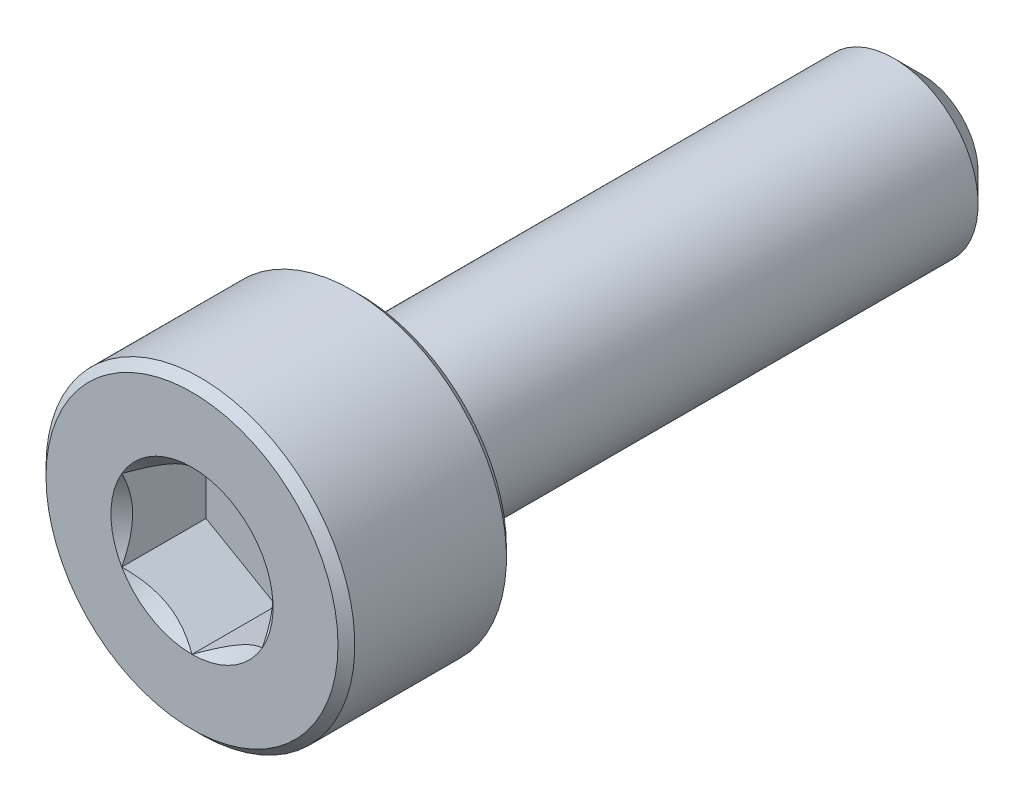
SolidWorks part; units mm, degrees
ref_plane "Front Plane" through (0, 0, 0) normal (0, 0, 1) x (1, 0, 0)
ref_plane "Top Plane" through (0, 0, 0) normal (0, 1, 0) x (1, 0, 0)
ref_plane "Right Plane" through (0, 0, 0) normal (1, 0, 0) x (0, 0, -1)
sketch "Sketch1" plane through (0, 0, 0) normal (1, 0, 0) x (0, 0, -1)
  line L0 (-6.5, 0) -> (6.5, 0) construction
  line L1 (6.5, 0) -> (6.5, 1) construction
  line L2 (6.5, 1) -> (6, 1.5) construction
  line L3 (6, 1.5) -> (-3.5, 1.5) construction
  line L5 (-3.5, 1.5) -> (-3.5, 2.75) construction
  line L6 (-3.5, 2.75) -> (-6.5, 2.75) construction
  line L7 (-6.5, 2.75) -> (-6.5, 0) construction
  line L8 (6.5, 1) -> (6.5, 1.5) construction
  line L9 (6.4688, 1.5541) -> (6.7188, 1.1211) construction
  line L10 (6.7188, 1.1211) -> (6.9688, 1.5541) construction
  line L11 (6.9688, 1.5541) -> (6.4688, 1.5541) construction
  line L12 (6.7188, 1.5541) -> (6.7188, 1.5) construction
  line L13 (6.7188, 1.1211) -> (6.7188, 1.1752) construction
  line L14 (6.6875, 1.1752) -> (6.75, 1.1752) construction
  line L15 (6.5, 1.5) -> (6.9375, 1.5) construction
  line L16 (6.4844, 1.5271) -> (6.9531, 1.5271) construction
  line L17 (6.5, 0) -> (6.5, -1.5) construction
  line L18 (-3.65, 2.75) -> (-3.5, 2.6) construction
  line L19 (-6.35, 2.75) -> (-6.5, 2.6) construction
  point P0 (-6.5, 1.25)
  point P3 (4.75, 1.5)
  point P4 (0, 0)
  point P22 (6.7188, 1.1752)
  point P24 (-3.5, 1.5)
  point P25 (6.7188, 1.5)
  point P28 (6.7188, 1.5271)
  point P29 (4.75, -1.5)
  point P31 (-5, 2.75)
  point P37 (-4.025, 2.75)
  point P38 (-6.275, 2.75)
  point P41 (-5, 0)
  dimension "head height" = 3
  dimension "D1" = 45
  dimension "Head Diameter" = 5.5
  dimension "Thread Size" = 3
  dimension "drive size" = 2.5
  dimension "Thread Pitch" = 0.5
  dimension "D2" = 0.0625
  dimension "D3" = 0.5
  dimension "D4" = 1.75
  dimension "D7" = 0.15
  dimension "D8" = 0.15
  dimension "D9" = 0.15
  dimension "D10" = 0.075
  dimension "D11" = 0.375
  dimension "length" = 10
  dimension "Drive Depth" = 1.5
sketch "Sketch2" plane through (0, 0, 0) normal (1, 0, 0) x (0, 0, -1)
  line L1 (-6.35, 2.75) -> (-3.65, 2.75)
  line L4 (6, 1.5) -> (6.5, 1)
  line L5 (6.5, 1) -> (6.5, 0)
  line L6 (-3.65, 2.75) -> (-3.5, 2.6) construction
  line L7 (6.5, 0) -> (-6.5, 0)
  line L8 (-6.35, 2.75) -> (-6.5, 2.6) construction
  line L9 (-3.65, 2.75) -> (-3.5, 2.6)
  line L10 (-6.35, 2.75) -> (-6.5, 2.6)
  line L11 (-6.5, 2.6) -> (-6.5, 0)
  line L12 (-3.5, 2.6) -> (-3.5, 1.5)
  line L13 (-3.5, 1.5) -> (6, 1.5)
revolve "Revolve1" add sketch "Sketch2" angle 360 about L7
sketch "Sketch3" plane through (0, 0, 6.5) normal (0, 0, 1) x (1, 0, 0)
  line L1 (0, 1.4434) -> (-1.25, 0.7217)
  line L2 (-1.25, 0.7217) -> (-1.25, -0.7217)
  line L3 (-1.25, -0.7217) -> (0, -1.4434)
  line L4 (0, -1.4434) -> (1.25, -0.7217)
  line L5 (1.25, -0.7217) -> (1.25, 0.7217)
  line L6 (1.25, 0.7217) -> (0, 1.4434)
  circle A0 centre (0, 0) radius 1.25 construction
  dimension "D1" = 2.5
extrude "Cut-Extrude1" cut sketch "Sketch3" against normal up to vertex (1.5 mm away) up to point (0, 0, 5)
sketch "Sketch4" plane through (0, 0, 6.5) normal (0, 0, 1) x (1, 0, 0)
  circle A0 centre (0, 0) radius 1.4434
extrude "Cut-Extrude2" cut sketch "Sketch4" against normal blind 0.5 draft 45
ref_plane "Plane1" [suppressed] through (0, 0, 3.5) normal (0, 0, 1) x (1, 0, 0)
split "Split1" [suppressed] bodies to split 106
sketch "Sketch6" [suppressed] plane through (0, 0, -6.5) normal (0, 0, -1) x (-1, 0, 0)
  circle A0 centre (0, 0) radius 1.5
curve "Helix/Spiral1" [suppressed] pitch 0.5 height 10.5 turns 21
sketch "Sketch7" [suppressed] plane through (0, 0, 0) normal (1, 0, 0) x (0, 0, -1)
  line L0 (6.4844, 1.5271) -> (6.9531, 1.5271)
  line L1 (6.9531, 1.5271) -> (6.75, 1.1752)
  line L2 (6.75, 1.1752) -> (6.6875, 1.1752)
  line L3 (6.6875, 1.1752) -> (6.4844, 1.5271)
sweep "Cut-Sweep1" [suppressed] cut profiles "Sketch7" path "Helix/Spiral1"
sketch "Sketch8" [suppressed] plane through (0, 0, 3.5) normal (0, 0, -1) x (-1, 0, 0)
  circle A0 centre (0, 0) radius 1.5
extrude "Boss-Extrude1" [suppressed] add sketch "Sketch8" along normal through all draft 45
ref_plane "Plane2" [suppressed] through (0, 0, 5) normal (0, 0, 1) x (1, 0, 0)
sketch "Sketch9" [suppressed] plane through (0, 0, 5) normal (0, 0, 1) x (1, 0, 0)
  line L0 (0, 2.6744) -> (0.072, 2.7491)
  line L1 (0, 2.6744) -> (-0.072, 2.7491)
  line L2 (0, 2.75) -> (0, 0) construction
  line L3 (-0.072, 2.7491) -> (0, 0) construction
  line L4 (0, 0) -> (0.072, 2.7491) construction
  arc A0 (0.072, 2.7491) -> (-0.072, 2.7491) centre (0, 0) ccw
  circle A1 centre (0, 0) radius 2.6744 construction
  dimension "D1" = 5.5
  dimension "D2" = 5.3487
  dimension "D3" = 3
extrude "Cut-Extrude4" [suppressed] cut sketch "Sketch9" against normal up to vertex and the other way up to vertex
pattern_circular "CirPattern2" [suppressed] count 96 over 360 about axis through (0, 0, 6.5) along (0, 0, -1) of bodies 113
equation "\"D2@Sketch1\" = \"Thread Pitch@Sketch1\" / 8"
equation "\"D3@Sketch1\" = \"Thread Pitch@Sketch1\""
equation "\"D3@Helix/Spiral1\" = \"length@Sketch1\" + \"Thread Pitch@Sketch1\""
equation "\"D4@Helix/Spiral1\" = \"Thread Pitch@Sketch1\""
equation "\"D4@Sketch1\" = \"Thread Pitch@Sketch1\" * 3.5"
equation "\"D7@Sketch1\"=\"head height@Sketch1\"*.05"
equation "\"D8@Sketch1\"=\"D7@Sketch1\""
equation "\"D9@Sketch1\"=\"D7@Sketch1\""
equation "\"D10@Sketch1\"=\"D7@Sketch1\"/2"
equation "\"D11@Sketch1\"=\"D10@Sketch1\"*5"
equation "\"D1@CirPattern2\"=( 360 / \"D3@Sketch9\" )*0.8"
equation "\"D1@Sketch3\" = \"drive size@Sketch1\""
equation "\"D2@Sketch9\"=\"Head Diameter@Sketch1\" * 0.9725"
